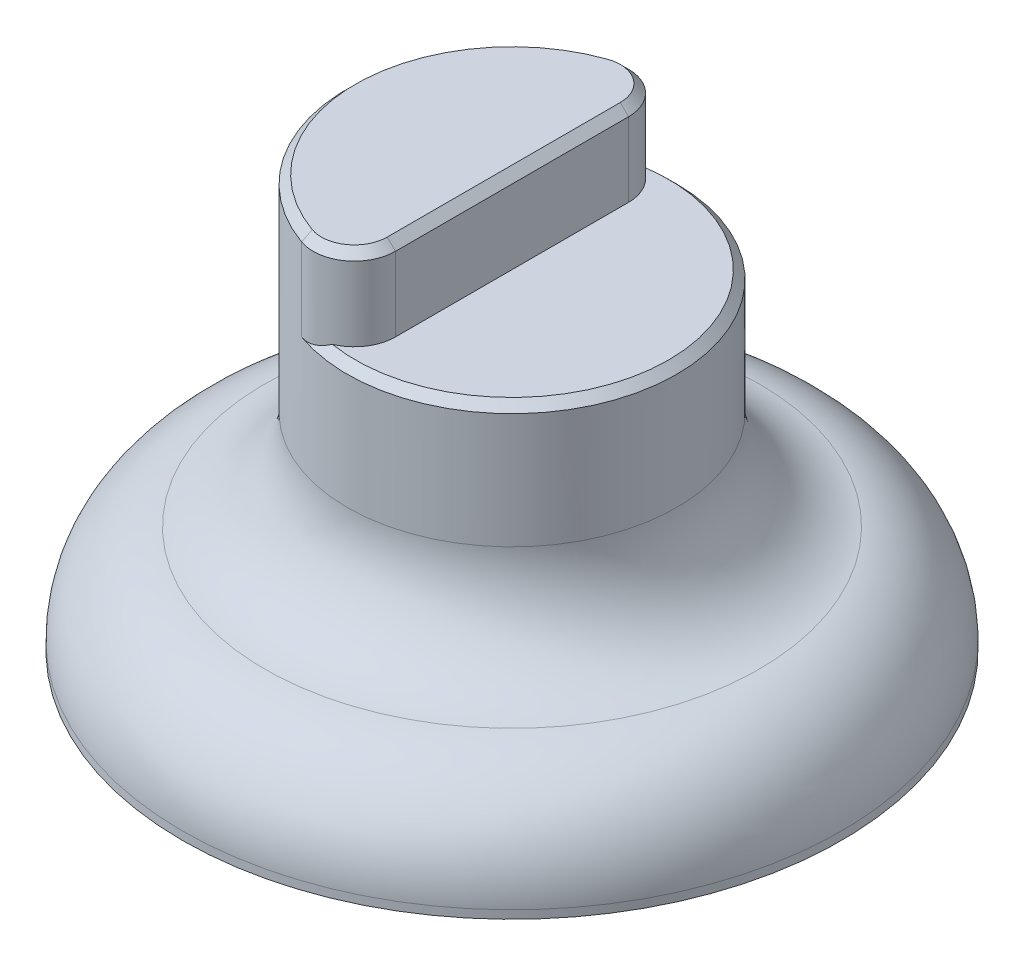
SolidWorks part; units mm, degrees
ref_plane "Front Plane" through (0, 0, 0) normal (0, 0, 1) x (1, 0, 0)
ref_plane "Top Plane" through (0, 0, 0) normal (0, 1, 0) x (1, 0, 0)
ref_plane "Right Plane" through (0, 0, 0) normal (1, 0, 0) x (0, 0, -1)
sketch "Sketch1" plane through (0, 0, 0) normal (0, 0, 1) x (1, 0, 0)
  line L0 (0, 0) -> (0, 40)
  line L1 (0, 40) -> (20, 40)
  line L2 (20, 40) -> (20, 25)
  line L3 (0, 0) -> (40, 0)
  line L4 (40, 0) -> (40, 1)
  arc A0 (20, 25) -> (30, 13) centre (32.2, 25) ccw
  arc A1 (40, 1) -> (30, 13) centre (27.8, 1) ccw
  point P10 (47.7501, 3)
  point P11 (20.2407, 9.8789)
  point P12 (20, 27.1255)
  dimension "D1" = 1
  dimension "D2" = 40
  dimension "D3" = 40
  dimension "D4" = 20
  dimension "D5" = 15
revolve "Revolve1" add sketch "Sketch1" angle 360 about L0
sketch "Sketch2" plane through (0, 40, 0) normal (0, 1, 0) x (1, 0, 0)
  line L0 (0, 20) -> (0, -20)
  circle A1 centre (0, 0) radius 20
  arc A2 (0, 20) -> (0, -20) centre (0, 0) ccw
  dimension "D1" = 0
extrude "Boss-Extrude1" add sketch "Sketch2" along normal blind 10
fillet "Fillet1" radius 5 2 edges at (0, 45, -20) (0, 45, 20)
chamfer "Chamfer1" distance 1 angle 45 5 edges at (0, 50, 0) (-2.1132, 50, -18.2246) (-2.1132, 50, 18.2246) (-20, 50, 0) (20, 40, 0)
